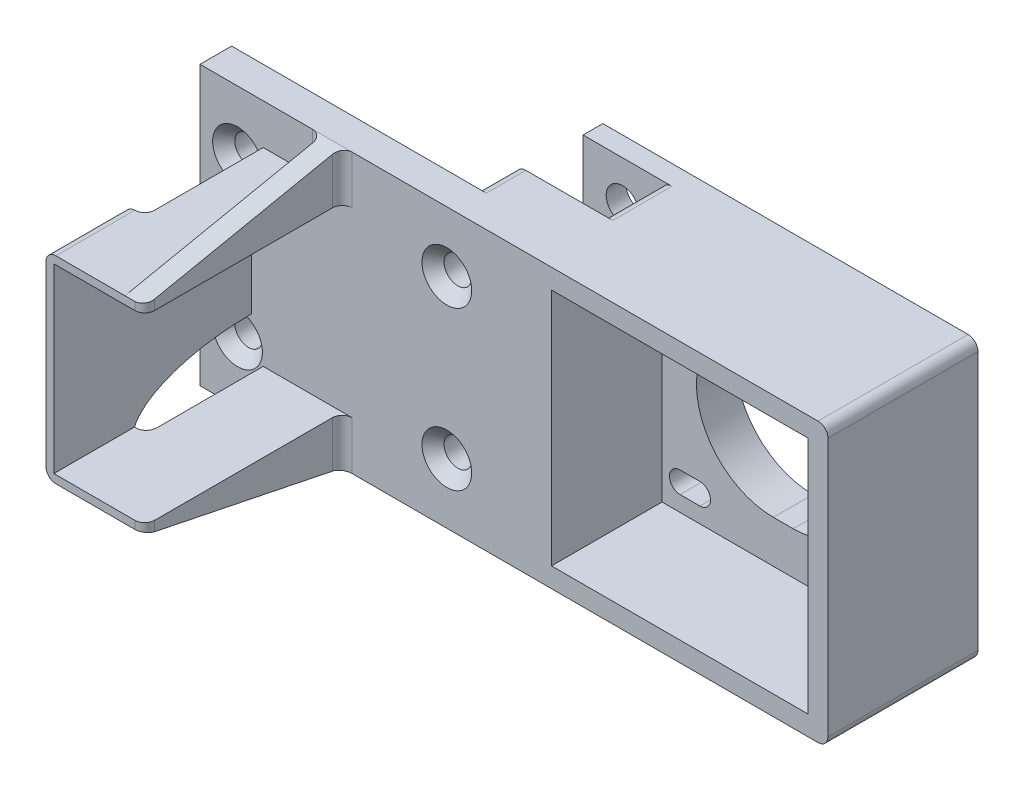
SolidWorks part; units mm, degrees
ref_plane "Front Plane" through (0, 0, 0) normal (0, 0, 1) x (1, 0, 0)
ref_plane "Top Plane" through (0, 0, 0) normal (0, 1, 0) x (1, 0, 0)
ref_plane "Right Plane" through (0, 0, 0) normal (1, 0, 0) x (0, 0, -1)
sketch "Sketch1" plane through (0, 0, 0) normal (0, 0, 1) x (1, 0, 0)
  line L1 (31, 106.401) -> (-31, 106.401) construction
  line L2 (31, 106.401) -> (31, 55.901) construction
  line L3 (31, 55.901) -> (-31, 55.901) construction
  line L4 (-31, 106.401) -> (-31, 55.901) construction
  line L5 (53, 116.401) -> (-36, 116.401)
  line L6 (53, 116.401) -> (53, 45.901)
  line L7 (53, 45.901) -> (-36, 45.901)
  line L8 (-36, 116.401) -> (-36, 45.901)
  circle A1 centre (26.5, 61.151) radius 2.5
  circle A2 centre (-26.5, 61.151) radius 2.5
  circle A3 centre (-26.5, 101.151) radius 2.5
  circle A4 centre (26.5, 101.151) radius 2.5
  dimension "D1" = 5
  dimension "D2" = 10
  dimension "D3" = 10
  dimension "D4" = 22
extrude "Boss-Extrude1" add sketch "Sketch1" along normal blind 8
sketch "Sketch2" plane through (53, 0, 0) normal (1, 0, 0) x (0, 0, -1)
  line L0 (-8, 45.901) -> (0, 45.901) construction
  line L1 (-8, 116.401) -> (30, 116.401)
  line L2 (-8, 116.401) -> (-8, 45.901)
  line L3 (-8, 45.901) -> (30, 45.901)
  line L4 (30, 116.401) -> (30, 45.901)
  dimension "D1" = 30
extrude "Boss-Extrude2" add sketch "Sketch2" against normal blind 5
sketch "Sketch3" plane through (0, 0, -30) normal (0, 0, -1) x (-1, 0, 0)
  line L0 (-48, 116.401) -> (-48, 45.901) construction
  line L1 (-53, 45.901) -> (-53, 116.401) construction
  line L2 (-48, 45.901) -> (-48, 116.401) construction
  line L3 (-48, 45.901) -> (-118, 45.901)
  line L4 (-48, 45.901) -> (-48, 116.401) construction
  line L5 (-48, 116.401) -> (-118, 116.401)
  line L6 (-118, 45.901) -> (-118, 116.401)
  line L7 (-53, 116.401) -> (36, 116.401) construction
  line L8 (-48, 116.401) -> (-28, 116.401)
  line L9 (-48, 116.401) -> (-48, 45.901) construction
  line L10 (-48, 45.901) -> (-28, 45.901)
  line L11 (-28, 116.401) -> (-28, 45.901)
  point P3 (-48, 81.151)
  point P7 (-48, 81.151)
  dimension "D2" = 65
  dimension "D3" = 20
extrude "Boss-Extrude3" add sketch "Sketch3" against normal blind 5
ref_plane "Plane1" through (0, 81.151, 0) normal (0, 1, 0) x (1, 0, 0)
sketch "Sketch17" plane through (0, 0, -25) normal (0, 0, 1) x (1, 0, 0)
  line L8 (118, 116.401) -> (53, 116.401)
  line L9 (118, 116.401) -> (53, 116.401)
  line L10 (53, 45.901) -> (118, 45.901)
  line L11 (53, 116.401) -> (53, 45.901)
  line L15 (53, 116.401) -> (53, 45.901)
  line L16 (53, 45.901) -> (118, 45.901)
  line L17 (118, 45.901) -> (118, 116.401)
  line L18 (118, 45.901) -> (118, 116.401)
  dimension "D1" = 0
extrude "Boss-Extrude6" add sketch "Sketch17" along normal blind 5
sketch "Sketch7" plane through (0, 0, -25) normal (0, 0, 1) x (1, 0, 0)
  line L0 (118, 81.151) -> (53, 81.151) construction
  line L1 (81.2, 100.651) -> (86.2, 100.651)
  line L2 (28, 45.901) -> (28, 116.401) construction
  line L3 (86.2, 61.651) -> (81.2, 61.651)
  line L4 (81.2, 81.151) -> (81.2, 104.781) construction
  line L6 (53, 45.901) -> (53, 116.401) construction
  line L7 (83.7, 71.0483) -> (83.7, 91.2537)
  line L8 (81.2, 104.781) -> (57.57, 104.781) construction
  line L9 (57.57, 107.481) -> (62.57, 107.481)
  line L10 (62.57, 102.081) -> (57.57, 102.081)
  line L11 (104.83, 102.081) -> (109.83, 102.081)
  line L12 (109.83, 107.481) -> (104.83, 107.481)
  line L13 (109.83, 54.821) -> (104.83, 54.821)
  line L14 (104.83, 60.221) -> (109.83, 60.221)
  line L15 (62.57, 60.221) -> (57.57, 60.221)
  line L16 (57.57, 54.821) -> (62.57, 54.821)
  line L17 (118, 45.901) -> (118, 116.401) construction
  circle A0 centre (38, 106.151) radius 4.15
  circle A1 centre (38, 56.151) radius 4.15
  circle A2 centre (81.2, 81.151) radius 19.5
  circle A3 centre (86.2, 81.151) radius 19.5
  arc A4 (57.57, 107.481) -> (57.57, 102.081) centre (57.57, 104.781) ccw
  arc A5 (62.57, 107.481) -> (62.57, 102.081) centre (62.57, 104.781) cw
  arc A6 (104.83, 107.481) -> (104.83, 102.081) centre (104.83, 104.781) ccw
  arc A7 (109.83, 107.481) -> (109.83, 102.081) centre (109.83, 104.781) cw
  arc A8 (109.83, 54.821) -> (109.83, 60.221) centre (109.83, 57.521) ccw
  arc A9 (104.83, 54.821) -> (104.83, 60.221) centre (104.83, 57.521) cw
  arc A10 (62.57, 54.821) -> (62.57, 60.221) centre (62.57, 57.521) ccw
  arc A11 (57.57, 54.821) -> (57.57, 60.221) centre (57.57, 57.521) cw
  point P10 (109.4, 81.151)
  point P19 (83.7, 81.151)
  dimension "D1" = 8.3
  dimension "D4" = 39
  dimension "D5" = 28.2
  dimension "D10" = 2.7
  dimension "D2" = 10
  dimension "D3" = 25
  dimension "D6" = 56.4
  dimension "D7" = 5
  dimension "D8" = 23.63
  dimension "D9" = 23.63
extrude "Cut-Extrude1" cut sketch "Sketch7" against normal up to next and the other way up to surface
sketch "Sketch8" plane through (0, 0, 8) normal (0, 0, 1) x (1, 0, 0)
  line L0 (26.5, 101.151) -> (26.5, 61.151) construction
  line L1 (26.5, 81.151) -> (-26.5, 81.151) construction
  line L2 (-26.5, 101.151) -> (-26.5, 61.151) construction
  line L3 (0, 104.6159) -> (0, 57.6861) construction
  line L4 (-23, 81.151) -> (23, 81.151) construction
  line L5 (-25, 56.151) -> (-25, 106.151)
  line L6 (-23, 58.151) -> (23, 58.151)
  line L7 (-23, 58.151) -> (-23, 104.151)
  line L8 (-23, 104.151) -> (23, 104.151)
  line L9 (23, 58.151) -> (23, 104.151)
  line L10 (-23, 58.151) -> (23, 104.151) construction
  line L11 (-23, 104.151) -> (23, 58.151) construction
  line L12 (-25, 106.151) -> (25, 106.151)
  line L13 (25, 56.151) -> (25, 106.151)
  line L14 (-25, 56.151) -> (25, 56.151)
  line L15 (0, 106.151) -> (0, 104.151)
  line L16 (0, 58.151) -> (0, 56.151)
  point P10 (0, 81.151)
  point P14 (0, 81.151)
  point P17 (0, 81.151)
  dimension "D1" = 46
  dimension "D2" = 46
  dimension "D4" = 23
  dimension "D5" = 23
  dimension "D3" = 2
extrude "Boss-Extrude4" add sketch "Sketch8" along normal blind 50
ref_plane "Plane2" through (0, 81.151, 0) normal (0, -1, 0) x (-1, 0, 0)
sketch "Sketch9" plane through (0, 81.151, 0) normal (0, -1, 0) x (-1, 0, 0)
  line L0 (25, -58) -> (36, -8)
rib "Rib2" sketch "Sketch9" sketch "Sketch9" thickness 5 extrusion direction parallel to sketch draft on no parameters "D1"=5
ref_plane "Plane3" through (-12.5, 0, 0) normal (1, 0, 0) x (0, 0, -1)
sketch "Sketch11" plane through (0, 0, 0) normal (1, 0, 0) x (0, 0, -1)
  line L0 (-58, 106.151) -> (-8, 116.401)
rib "Rib4" sketch "Sketch11" sketch "Sketch11" thickness 5 extrusion direction parallel to sketch draft on no parameters "D1"=5
mirror "Mirror2" about plane through (0, 81.151, 0) normal (0, -1, 0) of "Rib4"
sketch "Sketch12" plane through (-25, 0, 0) normal (-1, 0, 0) x (0, 0, 1)
  line L0 (58, 106.151) -> (8, 106.151) construction
  line L1 (8, 83.651) -> (8, 99.151) construction
  line L2 (38, 106.151) -> (8, 106.151)
  line L3 (8, 106.151) -> (8, 94.151)
  ellipse E0 centre (8, 106.151) end of major axis (38, 106.151) minor radius 12 (8, 94.151) -> (38, 106.151) ccw
  dimension "D1" = 30
  dimension "D2" = 12
extrude "Cut-Extrude2" cut sketch "Sketch12" against normal blind 5
mirror "Mirror3" about plane through (0, 81.151, 0) normal (0, -1, 0) of "Cut-Extrude2"
sketch "Sketch13" plane through (0, 0, 8) normal (0, 0, 1) x (1, 0, 0)
  point P0 (-26.5, 101.151)
  point P1 (-26.5, 61.151)
  point P3 (26.5, 61.151)
  point P5 (26.5, 101.151)
hole_wizard "CSK for M6 Countersunk Flat Head Screw1" positions "Sketch13" profile "Sketch14" countersink size "M6" standard "ISO"
sketch "Sketch14" plane through (-26.5, 101.151, 8) normal (1, 0, 0) x (0, -1, 0)
  line L0 (0, 0) -> (0, 10.103)
  line L1 (0, 10.103) -> (3.5, 8)
  line L2 (3.5, 8) -> (3.5, 2.8)
  line L3 (3.5, 2.8) -> (6.3, 0)
  line L5 (6.3, 0) -> (0, 0)
  line L6 (-3.5, 2.8) -> (-6.3, 0) construction
  line L10 (0, 10.103) -> (-3.5, 8) construction
  line L11 (0, -6.35) -> (0, 107.95) construction
  dimension "Hole Dia." = 7
  dimension "Hole Depth" = 8
  dimension "Near C'Sink Dia." = 12.6
  dimension "Near C'Sink Angle" = 90
  dimension "Drill Angle" = 118
sketch "Sketch15" plane through (0, 81.151, 0) normal (0, 1, 0) x (1, 0, 0)
  line L0 (36, 25) -> (36, 0)
  line L1 (53, 0) -> (-36, 0) construction
  line L2 (28, 25) -> (48, 25) construction
  line L3 (53, 0) -> (-36, 0) construction
  line L4 (48, 25) -> (48, 0) construction
  dimension "D1" = 12
rib "Rib5" sketch "Sketch15" sketch "Sketch15" thickness 5 extrusion direction parallel to sketch draft on no parameters "D1"=5
sketch "Sketch16" plane through (0, 45.901, 0) normal (0, -1, 0) x (1, 0, 0)
  line L0 (-36, 8) -> (-5, 8) construction
  line L1 (118, -30) -> (123, -30)
  line L2 (118, -30) -> (118, 8)
  line L3 (118, 8) -> (123, 8)
  line L4 (123, -30) -> (123, 8)
  dimension "D1" = 5
extrude "Boss-Extrude5" add sketch "Sketch16" against normal up to surface (70.5 mm away) up to face at (34.75, 116.401, -9.8333)
sketch "Sketch6" plane through (0, 116.401, 0) normal (0, 1, 0) x (1, 0, 0)
  line L0 (53, -8) -> (118, -8)
rib "Rib1" sketch "Sketch6" sketch "Sketch6" thickness 5 extrusion direction parallel to sketch draft on no parameters "D1"=5
sketch "Sketch19" plane through (0, 116.401, 0) normal (0, 1, 0) x (1, 0, 0)
  line L0 (48, 10) -> (26, 10)
  line L1 (48, 25) -> (48, 0) construction
  line L2 (26, 10) -> (26, 0)
  line L3 (26, 0) -> (48, 0)
  line L4 (48, 0) -> (48, 10)
  line L5 (48, 0) -> (-36, 0) construction
  dimension "D1" = 10
  dimension "D2" = 22
extrude "Boss-Extrude7" add sketch "Sketch19" against normal blind 7
mirror "Mirror5" about plane through (0, 81.151, 0) normal (0, 1, 0) of "Rib1"
mirror "Mirror6" about plane through (0, 81.151, 0) normal (0, 1, 0) of "Boss-Extrude7"
sketch "Sketch20" plane through (28, 0, 0) normal (-1, 0, 0) x (0, 0, 1)
  line L0 (-25, 45.901) -> (-25, 116.401) construction
  line L1 (-25, 30.901) -> (-55, 30.901)
  line L2 (-25, 30.901) -> (-25, 131.401)
  line L3 (-25, 131.401) -> (-55, 131.401)
  line L4 (-55, 30.901) -> (-55, 131.401)
  line L5 (-25, 45.901) -> (-30, 45.901) construction
  line L6 (-25, 116.401) -> (-30, 116.401) construction
  line L7 (-30, 45.901) -> (-30, 116.401) construction
  line L8 (-30, 37.901) -> (-51, 37.901)
  line L9 (-30, 37.901) -> (-30, 124.401)
  line L10 (-30, 124.401) -> (-51, 124.401)
  line L11 (-51, 37.901) -> (-51, 124.401)
  point P8 (-27.5, 45.901)
  dimension "D1" = 15
  dimension "D2" = 15
  dimension "D3" = 30
  dimension "D4" = 8
  dimension "D5" = 8
  dimension "D6" = 4
extrude "Boss-Extrude8" [suppressed] add sketch "Sketch20" along normal blind 7
fillet "Fillet1" radius 2.5 8 edges at (48, 83.651, -12.5) (48, 78.651, -12.5) (36, 83.651, -12.5) (42, 83.651, 0) (42, 78.651, 0) (42, 78.651, -25) (42, 83.651, -25) (36, 78.651, -12.5)
fillet "Fillet2" radius 2.5 20 edges at (0, 110.276, 8) (0, 105.151, 58) (0, 52.026, 8) (0, 57.151, 58) (48, 116.401, -17.5) (48, 45.901, -17.5) (123, 45.901, -11) (123, 116.401, -11) (-5, 51.026, 8) (-30.5, 78.651, 8) (-30.5, 83.651, 8) (-5, 111.276, 8) (-20, 57.1545, 37.8949) (-20, 105.1475, 37.8949) (-25, 56.151, 48) (-25, 106.151, 48) (26, 109.401, -5) (26, 116.401, -5) (26, 52.901, -5) (26, 45.901, -5)
fillet "Fillet3" [suppressed] radius 2.5
